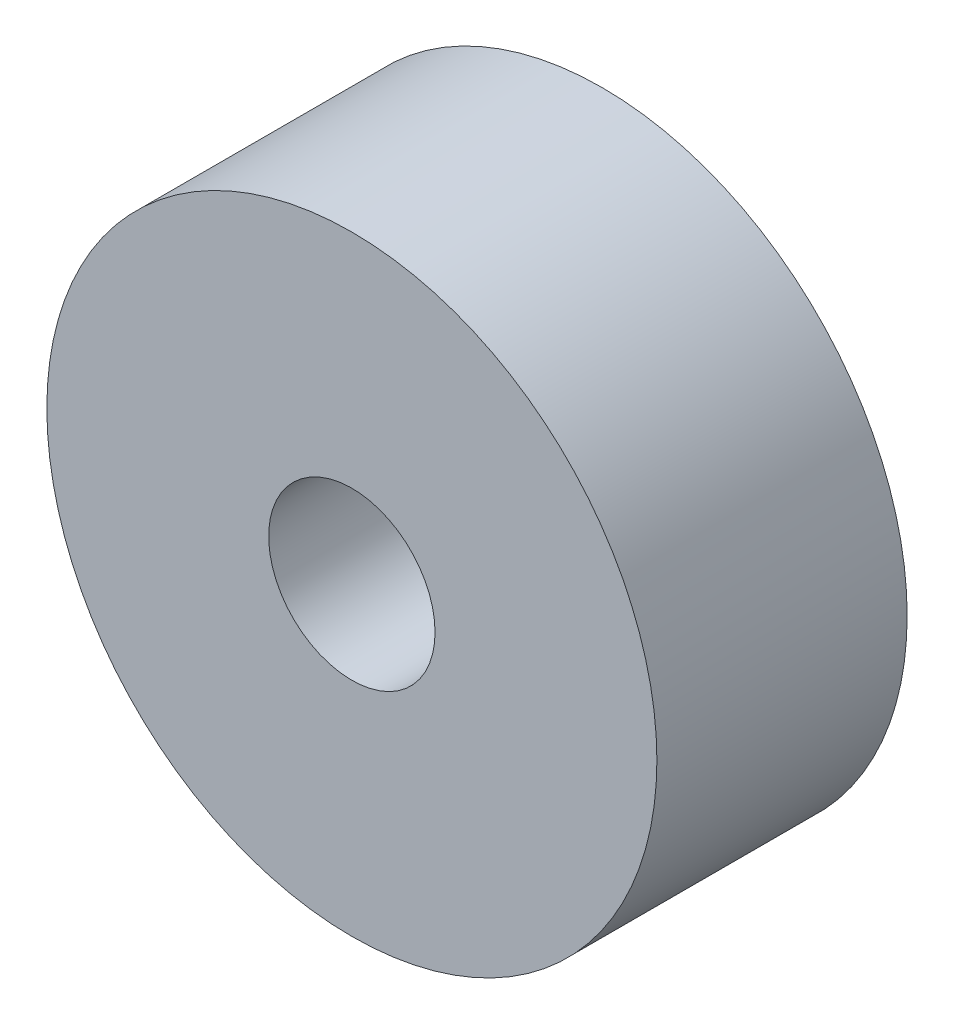
SolidWorks part; units mm, degrees
material "AISI 1020"
ref_plane "Спереди" through (0, 0, 0) normal (0, 0, 1) x (1, 0, 0)
ref_plane "Сверху" through (0, 0, 0) normal (0, 1, 0) x (1, 0, 0)
ref_plane "Справа" through (0, 0, 0) normal (1, 0, 0) x (0, 0, -1)
sketch "Эскиз1" plane through (0, 0, 0) normal (0, 0, 1) x (1, 0, 0)
  circle A0 centre (0, 0) radius 7.9 construction
  circle A1 centre (0, 0) radius 7.9
  circle A2 centre (0, 0) radius 22
  arc A3 (21.3772, 5.1978) -> (-21.3772, 5.1978) centre (0, 0) ccw construction
  dimension "D1" = 44
extrude "Бобышка-Вытянуть1" add sketch "Эскиз1" along normal up to surface (9.05 mm away)
sketch "Эскиз2" plane through (0, 0, 9.05) normal (0, 0, 1) x (1, 0, 0)
  circle A0 centre (-0.0002, 0.0002) radius 6 construction
  circle A1 centre (-0.0002, 0.0002) radius 6
  circle A2 centre (0, 0) radius 22 construction
  circle A3 centre (0, 0) radius 22
extrude "Бобышка-Вытянуть2" add sketch "Эскиз2" along normal offset from surface (9 mm away) 1 offset beyond the face yes
